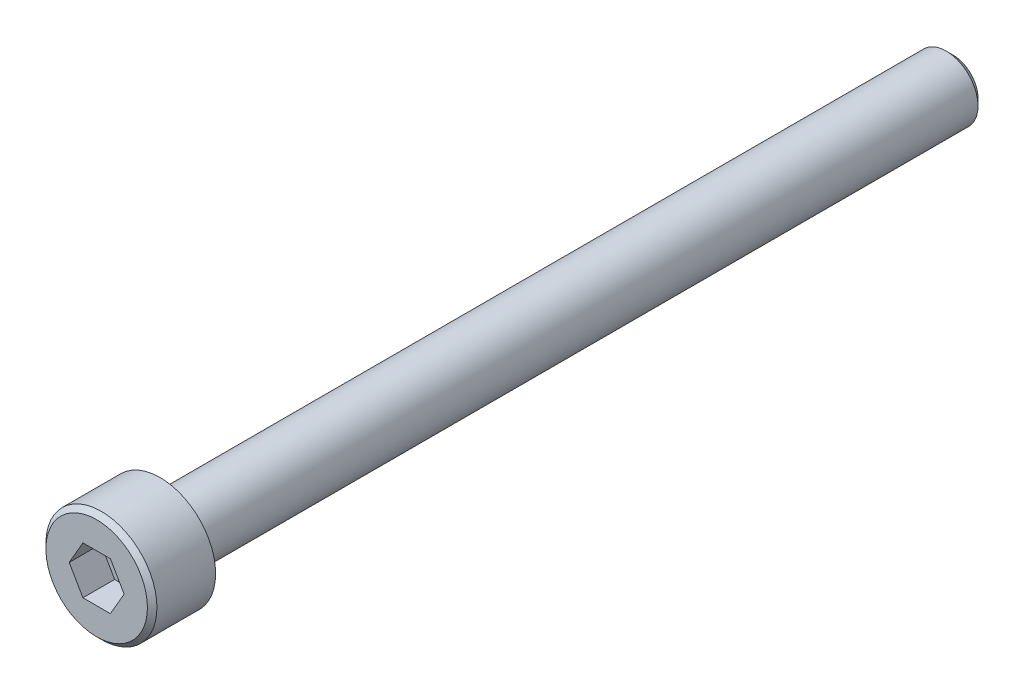
SolidWorks part; units mm, degrees
ref_plane "前视基准面" through (0, 0, 0) normal (0, 0, 1) x (1, 0, 0)
ref_plane "上视基准面" through (0, 0, 0) normal (0, 1, 0) x (1, 0, 0)
ref_plane "右视基准面" through (0, 0, 0) normal (1, 0, 0) x (0, 0, -1)
sketch "草图1" plane through (0, 0, 0) normal (1, 0, 0) x (0, 0, -1)
  line L0 (-4, 0) -> (-4, 3.2)
  line L1 (-4, 3.2) -> (-3.7, 3.5)
  line L2 (-3.7, 3.5) -> (0, 3.5)
  line L3 (0, 3.5) -> (0, 2)
  line L4 (0, 2) -> (49.5705, 2)
  line L5 (49.5705, 2) -> (50, 1.5705)
  line L6 (50, 1.5705) -> (50, 0)
  line L7 (50, 0) -> (-4, 0)
  line L8 (50, 0) -> (-4, 0) construction
revolve "旋转1" add sketch "草图1" angle 360 about L8 reverse direction yes
cosmetic thread "装饰螺纹线1"
ref_plane "基准面4" through (0, 0, 4) normal (0, 0, 1) x (1, 0, 0)
sketch "草图2" plane through (0, 0, 4) normal (0, 0, 1) x (1, 0, 0)
  line L0 (-0.866, -1.5) -> (0.866, -1.5)
  line L1 (0.866, -1.5) -> (1.7321, 0)
  line L2 (1.7321, 0) -> (0.866, 1.5)
  line L3 (0.866, 1.5) -> (-0.866, 1.5)
  line L4 (-0.866, 1.5) -> (-1.7321, 0)
  line L5 (-1.7321, 0) -> (-0.866, -1.5)
extrude "切除-拉伸1" cut sketch "草图2" against normal blind 2
ref_plane "基准面5" through (0, 0, 0) normal (0, 0, 1) x (1, 0, 0)
ref_plane "CP XY" through (0, 0, 0) normal (0, 0, -1) x (-1, 0, 0)
ref_plane "CP XZ" through (0, 0, 0) normal (0, 1, 0) x (1, 0, 0)
ref_plane "CP YZ" through (0, 0, 0) normal (1, 0, 0) x (0, 0, -1)
ref_axis "CP X" through (-80.9, 0, 0) along (1, 0, 0)
ref_axis "CP Y" through (0, 50, 0) along (0, -1, 0)
ref_axis "CP Z" through (0, 0, -80.9) along (0, 0, 1)
sketch3d "CP"
  point P0 (0, 0, 0)
